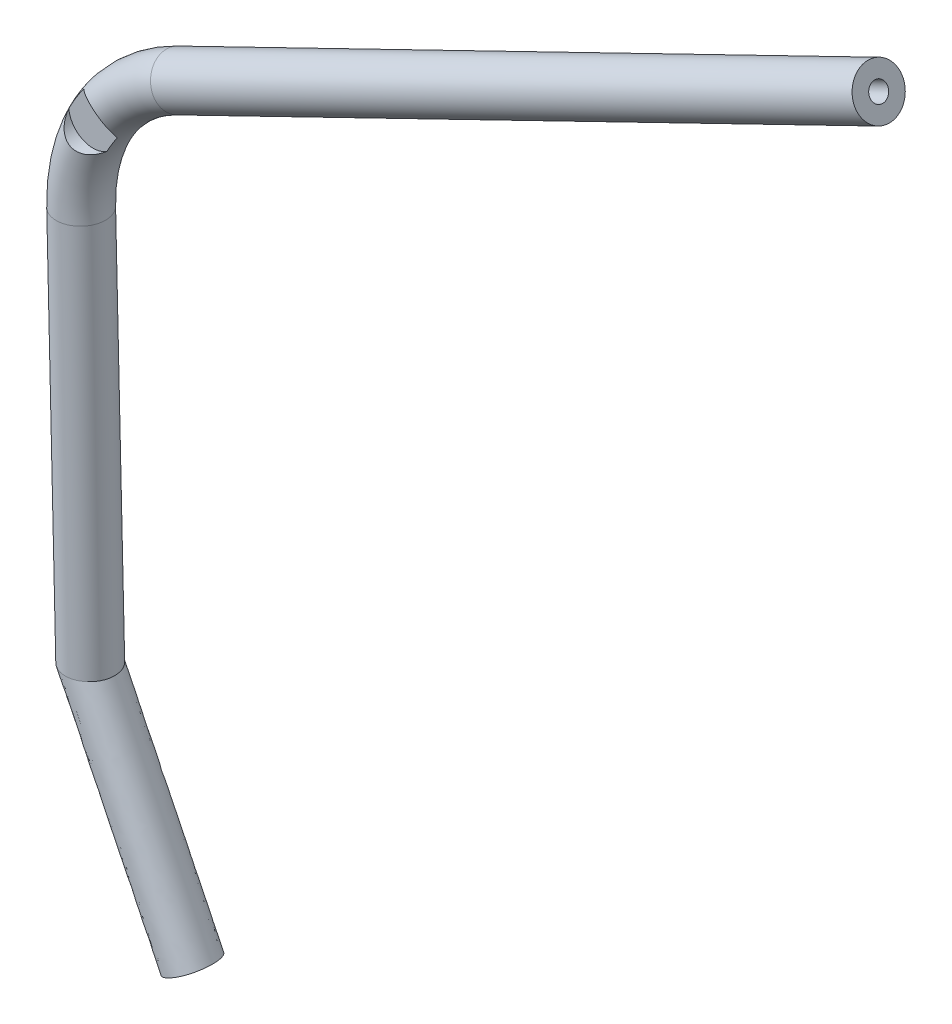
SolidWorks part; units mm, degrees
material "Cast Carbon Steel"
ref_plane "Front Plane" through (0, 0, 0) normal (0, 0, 1) x (1, 0, 0)
ref_plane "Top Plane" through (0, 0, 0) normal (0, 1, 0) x (1, 0, 0)
ref_plane "Right Plane" through (0, 0, 0) normal (1, 0, 0) x (0, 0, -1)
sketch "Sketch4" plane through (0, 0, 0) normal (0, 0, 1) x (1, 0, 0)
  arc A0 (-38.8747, 79.9498) -> (-88.8758, -2.0729) centre (0, 0) ccw
  dimension "D1" = 88.9
sketch "Sketch5" plane through (0, 0, 0) normal (0, 1, 0) x (1, 0, 0)
  circle A0 centre (-88.8758, 0) radius 12.7
  circle A1 centre (-88.8758, 0) radius 4.7625
  dimension "D1" = 25.4
  dimension "D2" = 7.9375
sweep "Sweep1" add profiles "Sketch5" path "Sketch4"
ref_plane "Plane4" through (0, 0, 0) normal (0.8993, 0.4373, 0) x (0, 0, -1)
sketch "Sketch6" plane through (0, 0, 0) normal (0.8993, 0.4373, 0) x (0, 0, -1)
  circle A0 centre (0, 88.8758) radius 12.7
  circle A1 centre (0, 88.8758) radius 4.7625
  circle A2 centre (0, 88.8758) radius 12.7 construction
  dimension "D1" = 7.9375
extrude "Boss-Extrude3" add sketch "Sketch6" along normal blind 406.4
ref_plane "Plane5" through (0, 0, 0) normal (0.0233, -0.9997, 0) x (-0.9997, -0.0233, 0)
sketch "Sketch7" plane through (0, 0, 0) normal (0.0233, -0.9997, 0) x (-0.9997, -0.0233, 0)
  circle A0 centre (88.8758, 0) radius 12.7
  circle A1 centre (88.8758, 0) radius 4.7625
  dimension "D1" = 7.9375
extrude "Boss-Extrude4" add sketch "Sketch7" along normal blind 203.2
ref_plane "Plane6" through (0, 0, 12.7) normal (0, 0, 1) x (1, 0, 0)
sketch "Sketch8" plane through (0, 0, 12.7) normal (0, 0, 1) x (1, 0, 0)
  line L0 (-76.1551, -1.7762) -> (-101.5482, -2.3685) construction
  line L1 (-33.3106, 68.5067) -> (-44.4176, 91.3495) construction
  circle A0 centre (-76.2699, 46.4942) radius 12.7
  dimension "D1" = 25.4
  dimension "D2" = 48.26
  dimension "D3" = 48.26
extrude "Cut-Extrude1" cut sketch "Sketch8" against normal blind 6.35
ref_plane "Plane7" through (4.7381, -203.1448, 0) normal (0.0233, -0.9997, 0) x (-0.9997, -0.0233, 0)
sketch "Sketch9" plane through (4.7381, -203.1448, 0) normal (0.0233, -0.9997, 0) x (-0.9997, -0.0233, 0)
  circle A0 centre (88.8758, 0) radius 12.7
  circle A1 centre (88.8758, 0) radius 4.7625
  dimension "D1" = 7.9375
sketch "Sketch11" plane through (0, 0, 0) normal (0, 0, 1) x (1, 0, 0)
  line L0 (-84.1136, -205.2171) -> (-28.5784, -319.4311)
  line L1 (6.1089, -12.5635) -> (-6.1089, 12.5635) construction
  dimension "D1" = 127
sweep "Sweep2" add profiles "Sketch9" path "Sketch11"
sketch "Sketch16" plane through (0, 0, 0) normal (0, 0, 1) x (1, 0, 0)
  line L0 (-41.2749, -319.7272) -> (-20.5045, -309.6279)
  line L1 (-15.8818, -319.135) -> (-71.417, -204.921) construction
  line L2 (-20.5045, -309.6279) -> (-15.8818, -319.135)
  line L3 (-15.8818, -319.135) -> (-41.2749, -319.7272)
  line L4 (6.1089, -12.5635) -> (-6.1089, 12.5635) construction
extrude "Cut-Extrude2" cut sketch "Sketch16" against normal through all both and the other way through all
